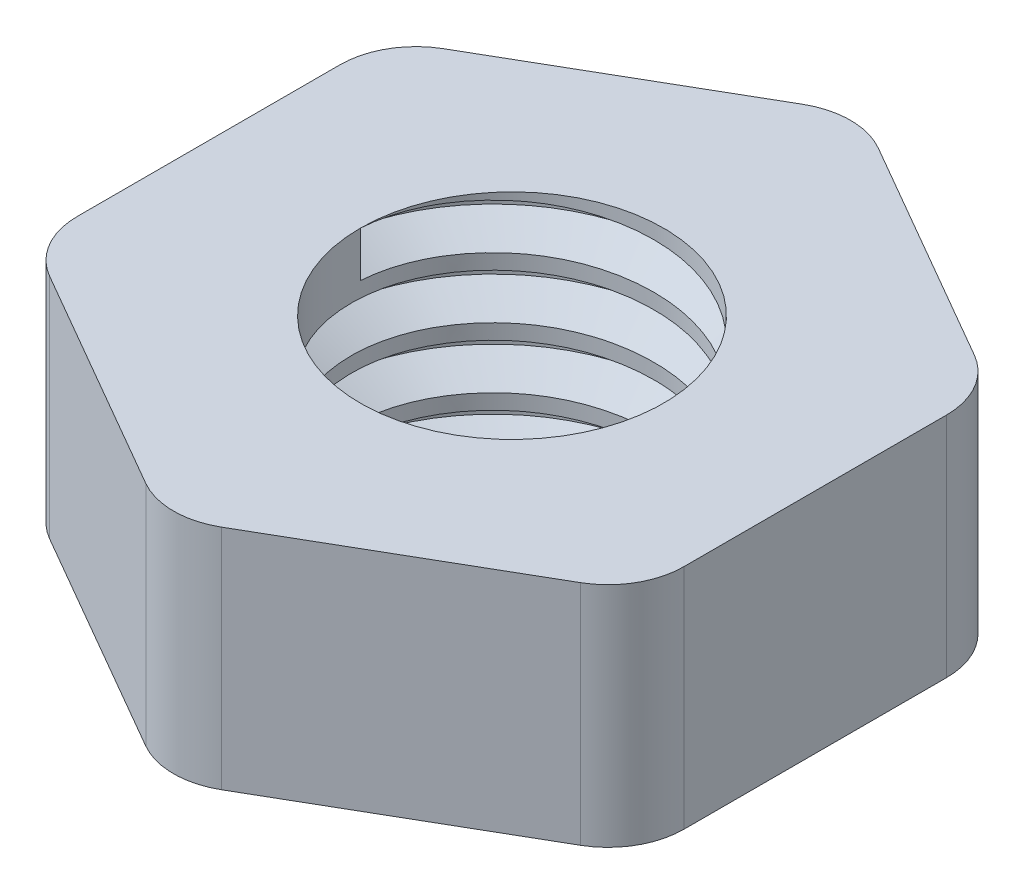
SolidWorks part; units mm, degrees
material "Alloy Steel"
ref_plane "Front Plane" through (0, 0, 0) normal (0, 0, 1) x (1, 0, 0)
ref_plane "Top Plane" through (0, 0, 0) normal (0, 1, 0) x (1, 0, 0)
ref_plane "Right Plane" through (0, 0, 0) normal (1, 0, 0) x (0, 0, -1)
sketch "Sketch1" plane through (0, 0, 0) normal (0, 1, 0) x (1, 0, 0)
  line L1 (0, -7.3323) -> (6.35, -3.6662)
  line L2 (6.35, -3.6662) -> (6.35, 3.6662)
  line L3 (6.35, 3.6662) -> (0, 7.3323)
  line L4 (0, 7.3323) -> (-6.35, 3.6662)
  line L5 (-6.35, 3.6662) -> (-6.35, -3.6662)
  line L6 (-6.35, -3.6662) -> (0, -7.3323)
  circle A0 centre (0, 0) radius 6.35 construction
  point P1 (0, 0)
  dimension "D1" = 12.7
extrude "Boss-Extrude1" add sketch "Sketch1" along normal blind 4.7625
sketch "Sketch2" plane through (0, 4.7625, 0) normal (0, 1, 0) x (1, 0, 0)
  circle A0 centre (0, 0) radius 3.175
  dimension "D1" = 6.35
extrude "Cut-Extrude1" cut sketch "Sketch2" against normal through all
thread "Thread1" pitch 1.27 method cut profile "Thread Profile1" start angle 0, offset 0, length 25.4, pitch 1.27, diameter 6.35
ref_plane "Plane1" through (-3.175, 4.7625, 0) normal (0, 0, 1) x (-1, 0, 0)
sketch "Thread Profile1" plane through (-3.175, 4.7625, 0) normal (0, 0, 1) x (-1, 0, 0)
  line L0 (0, 0) -> (0, 1.27) construction
  line L1 (0, 0) -> (0.6874, 0.3969)
  line L2 (0.6874, 0.3969) -> (0.6874, 0.5556)
  line L3 (0.6874, 0.5556) -> (0, 0.9525)
  line L4 (0.6874, 0.4762) -> (0, 0.4762) construction
  line L11 (0, 0) -> (0, 0.9525)
  point P2 (0, 0)
  dimension "Pitch" = 1.27
  dimension "Profile_Angle" = 60
  dimension "Profile_Land" = 0.1588
  dimension "Profile_Height" = 0.6874
fillet "Fillet1" radius 1.5875 6 edges at (-6.35, 2.3813, 3.6662) (-6.35, 2.3813, -3.6662) (0, 2.3813, -7.3323) (6.35, 2.3813, -3.6662) (6.35, 2.3813, 3.6662) (0, 2.3813, 7.3323)
